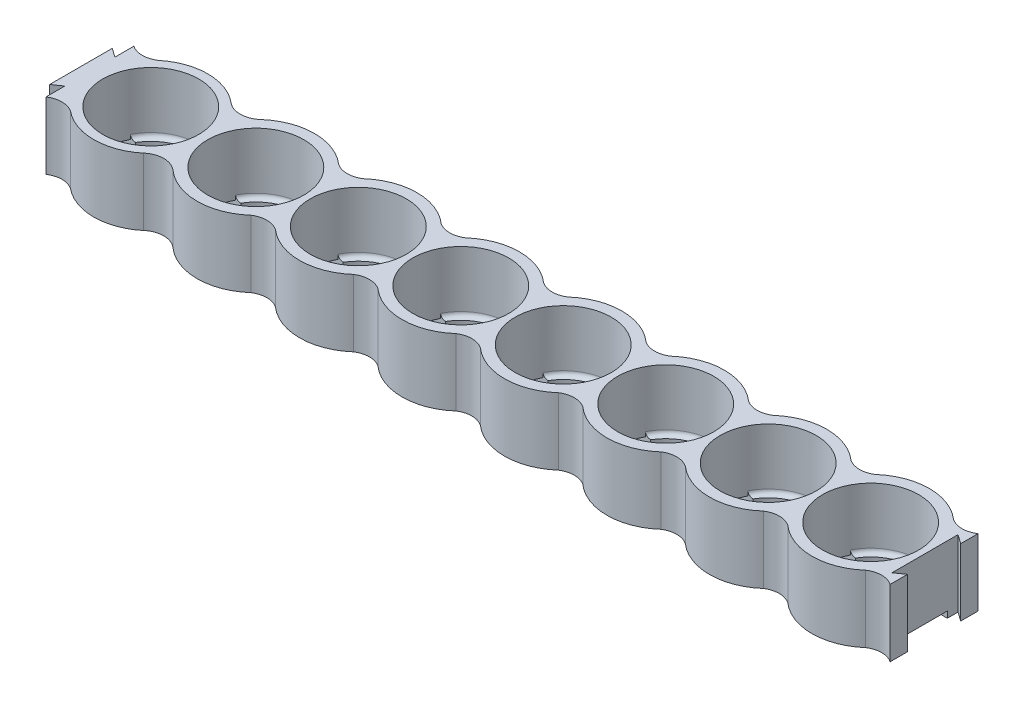
SolidWorks part; units mm, degrees
ref_plane "Front Plane" through (0, 0, 0) normal (0, 0, 1) x (1, 0, 0)
ref_plane "Top Plane" through (0, 0, 0) normal (0, 1, 0) x (1, 0, 0)
ref_plane "Right Plane" through (0, 0, 0) normal (1, 0, 0) x (0, 0, -1)
sketch "Sketch1" plane through (0, 0, 0) normal (0, 1, 0) x (1, 0, 0)
  line L0 (-80.5, 0) -> (80.5, 0) construction
  line L1 (0.2917, 8.9995) -> (0.2917, -8.9995) construction
  line L2 (94.6959, 9.8156) -> (94.6959, 5.9552)
  line L3 (-94.1126, 9.8156) -> (-94.1126, 5.5996)
  line L4 (-96.1126, 7) -> (-96.1126, -7)
  line L9 (-96.1126, 7) -> (-94.1126, 5.5996)
  line L10 (-96.1126, -7) -> (-94.1126, -5.5996)
  line L11 (94.6959, -5.9552) -> (94.6959, -9.8156)
  line L12 (92.6552, 7.3842) -> (95.0676, 5.695) construction
  line L13 (-94.1126, -5.5996) -> (-94.1126, -9.8156)
  line L14 (92.8552, 7) -> (92.8552, -7) construction
  line L15 (92.8552, 7) -> (94.8552, 5.5996) construction
  line L16 (92.8552, -7) -> (94.8552, -5.5996) construction
  line L17 (92.6552, 7.3842) -> (94.6959, 5.9552)
  line L18 (92.6552, 7.3842) -> (92.6552, -7.3842)
  line L19 (92.6552, -7.3842) -> (94.6959, -5.9552)
  line L20 (92.6552, -7.3842) -> (94.9699, -5.7634) construction
  line L21 (94.6959, 5.9552) -> (94.6959, -5.9552) construction
  line L22 (92.8552, 7) -> (94.9529, 5.5312) construction
  line L23 (92.8552, -7) -> (94.8552, -5.5996) construction
  circle A0 centre (-80.5, 0) radius 10.75
  arc A2 (-65.7207, -9.8156) -> (-48.2793, -9.8156) centre (-57, 0) ccw
  circle A3 centre (-57, 0) radius 10.75
  arc A4 (-72.3626, 9.8156) -> (-65.7207, 9.8156) centre (-69.0417, 13.5534) ccw
  arc A5 (-72.3626, -9.8156) -> (-65.7207, -9.8156) centre (-69.0417, -13.5534) cw
  arc A6 (-65.7207, -9.8156) -> (-48.2793, -9.8156) centre (-57, 0) ccw
  circle A7 centre (-34.0833, 0) radius 10.75
  arc A8 (-72.3626, 9.8156) -> (-88.6374, 9.8156) centre (-80.5, 0) ccw
  arc A9 (-42.8041, 9.8156) -> (-48.2793, 9.8156) centre (-45.5417, 13.9995) cw
  arc A10 (-42.8041, -9.8156) -> (-48.2793, -9.8156) centre (-45.5417, -13.9995) ccw
  arc A11 (-48.2793, 9.8156) -> (-65.7207, 9.8156) centre (-57, 0) ccw
  arc A12 (-48.2793, 9.8156) -> (-65.7207, 9.8156) centre (-57, 0) ccw
  arc A13 (-25.3626, 9.8156) -> (-42.8041, 9.8156) centre (-34.0833, 0) ccw
  arc A14 (-42.8041, -9.8156) -> (-25.3626, -9.8156) centre (-34.0833, 0) ccw
  arc A15 (-19.8874, -9.8156) -> (-25.3626, -9.8156) centre (-22.625, -13.9995) ccw
  arc A16 (-19.8874, 9.8156) -> (-25.3626, 9.8156) centre (-22.625, 13.9995) cw
  circle A17 centre (-11.1667, 0) radius 10.75
  arc A18 (-2.4459, 9.8156) -> (-19.8874, 9.8156) centre (-11.1667, 0) ccw
  arc A19 (-19.8874, -9.8156) -> (-2.4459, -9.8156) centre (-11.1667, 0) ccw
  arc A20 (3.0293, -9.8156) -> (-2.4459, -9.8156) centre (0.2917, -13.9995) ccw
  arc A21 (3.0293, 9.8156) -> (-2.4459, 9.8156) centre (0.2917, 13.9995) cw
  circle A22 centre (11.75, 0) radius 10.75
  arc A23 (20.4707, 9.8156) -> (3.0293, 9.8156) centre (11.75, 0) ccw
  arc A24 (3.0293, -9.8156) -> (20.4707, -9.8156) centre (11.75, 0) ccw
  arc A25 (25.9459, -9.8156) -> (20.4707, -9.8156) centre (23.2083, -13.9995) ccw
  arc A26 (25.9459, 9.8156) -> (20.4707, 9.8156) centre (23.2083, 13.9995) cw
  circle A27 centre (34.6667, 0) radius 10.75
  arc A28 (43.3874, 9.8156) -> (25.9459, 9.8156) centre (34.6667, 0) ccw
  arc A29 (25.9459, -9.8156) -> (43.3874, -9.8156) centre (34.6667, 0) ccw
  arc A30 (48.8626, -9.8156) -> (43.3874, -9.8156) centre (46.125, -13.9995) ccw
  arc A31 (48.8626, 9.8156) -> (43.3874, 9.8156) centre (46.125, 13.9995) cw
  circle A32 centre (57.5833, 0) radius 10.75
  arc A33 (66.3041, 9.8156) -> (48.8626, 9.8156) centre (57.5833, 0) ccw
  arc A34 (48.8626, -9.8156) -> (66.3041, -9.8156) centre (57.5833, 0) ccw
  arc A35 (71.7793, -9.8156) -> (66.3041, -9.8156) centre (69.0417, -13.9995) ccw
  arc A36 (71.7793, 9.8156) -> (66.3041, 9.8156) centre (69.0417, 13.9995) cw
  circle A37 centre (80.5, 0) radius 10.75
  arc A38 (89.2207, 9.8156) -> (71.7793, 9.8156) centre (80.5, 0) ccw
  arc A39 (71.7793, -9.8156) -> (89.2207, -9.8156) centre (80.5, 0) ccw
  arc A40 (94.6959, -9.8156) -> (89.2207, -9.8156) centre (91.9583, -13.9995) ccw
  arc A41 (94.6959, 9.8156) -> (89.2207, 9.8156) centre (91.9583, 13.9995) cw
  arc A42 (-94.1126, 9.8156) -> (-88.6374, 9.8156) centre (-91.375, 13.9995) ccw
  arc A43 (-94.1126, -9.8156) -> (-88.6374, -9.8156) centre (-91.375, -13.9995) cw
  arc A44 (-88.6374, -9.8156) -> (-72.3626, -9.8156) centre (-80.5, 0) ccw
  circle A45 centre (-80.5, 0) radius 9.75
  circle A46 centre (-57, 0) radius 9.75
  circle A47 centre (-34.0833, 0) radius 9.75
  circle A48 centre (-11.1667, 0) radius 9.75
  circle A49 centre (11.75, 0) radius 9.75
  circle A50 centre (34.6667, 0) radius 9.75
  circle A51 centre (57.5833, 0) radius 9.75
  circle A52 centre (80.5, 0) radius 9.75
  point P4 (94.6959, 0)
  point P26 (-96.1126, 0)
  point P30 (0, 0)
  point P43 (94.6959, -6.2842)
  point P84 (92.8552, 0)
  point P87 (92.5659, -7.8842)
  point P88 (0, 0)
  point P92 (94.7659, 6.0996)
  point P96 (92.4203, 7.8842)
  point P97 (0, 0)
  point P98 (94.6203, 6.0996)
  point P99 (92.4203, 7.8842)
  point P100 (92.4203, -7.8842)
  point P101 (92.6203, -7.5)
  point P102 (94.6203, -6.2908)
  point P103 (92.6203, -7.5)
  point P104 (94.6203, -6.0996)
  point P106 (94.6959, -6.2908)
  point P107 (94.6203, 6.0996)
  point P108 (94.6959, 6.2908)
  point P109 (92.6203, 7.5)
  point P110 (0, 0)
  dimension "D1" = 21.5
  dimension "D4" = 5
  dimension "D2" = 23.5
  dimension "D3" = 2
  dimension "D6" = 161
  dimension "D7" = 14
  dimension "D8" = 2
  dimension "D9" = 55
  dimension "D10" = 14
  dimension "D11" = 55
  dimension "D12" = 2
  dimension "D13" = 55
  dimension "D14" = 2
  dimension "D15" = 0.2
  dimension "D16" = 1
  dimension "D5" = 7
extrude "Boss-Extrude1" add sketch "Sketch1" along normal blind 15 contours A43 A44 A5 A2 A10 A14 A15 A19 A20 A24 A25 A29 A30 A34 A35 A39 A40 L11 L19 L18 L17 L2 A41 A38 A36 A33 A31 A28 A26 A23 A21 A18 A16 A13 A9 A11 A4 A8 A42 L3 L9 L4 L10 L13 A0 A3 A7 region at (92.7699, 0, -7.8854)
extrude "Boss-Extrude2" add sketch "Sketch1<3>" along normal blind 1.4 contours A0 A45 | A3 A46 | A7 A47 | A17 A48 | A22 A49 | A27 A50 | A32 A51 | A37 A52 region at (-90.9459, 0, 0) region at (-67.4459, 0, 0) region at (-44.5293, 0, 0) region at (-21.6126, 0, 0) region at (1.3041, 0, 0) region at (24.2207, 0, 0) region at (47.1374, 0, 0) region at (70.0541, 0, 0)
sketch "Sketch1<3>" plane through (0, 0, 0) normal (0, 1, 0) x (1, 0, 0) same geometry as "Sketch1"
sketch "Sketch2" plane through (0, 0, 0) normal (0, -1, 0) x (1, 0, 0)
  line L0 (-96.1126, -7) -> (-96.1126, 7) construction
  line L1 (-96.1126, 5) -> (92.6552, 5)
  line L2 (-96.1126, 5) -> (-96.1126, -5)
  line L3 (-96.1126, -5) -> (92.6552, -5)
  line L4 (92.6552, 5) -> (92.6552, -5)
  line L5 (-1.7287, -5) -> (-1.7287, 5) construction
  line L6 (-96.1126, 0) -> (92.6552, 0) construction
  line L7 (92.6552, -7.3842) -> (92.6552, 7.3842) construction
  point P8 (0, 0)
  point P360 (-1.7287, 0)
  dimension "D1" = 10
extrude "Cut-Extrude1" cut sketch "Sketch2" against normal blind 1.4
fillet "Fillet1" radius 1 16 edges at (80.5, 1.4, 10.75) (80.5, 1.4, -10.75) (-80.5, 1.4, 10.75) (-80.5, 1.4, -10.75) (-57, 1.4, 10.75) (-57, 1.4, -10.75) (-34.0833, 1.4, 10.75) (-34.0833, 1.4, -10.75) (-11.1667, 1.4, 10.75) (-11.1667, 1.4, -10.75) (11.75, 1.4, -10.75) (11.75, 1.4, 10.75) (34.6667, 1.4, 10.75) (34.6667, 1.4, -10.75) (57.5833, 1.4, -10.75) (57.5833, 1.4, 10.75)
equation "\"D2@Sketch1\"=\"D1@Sketch1\"+2"
